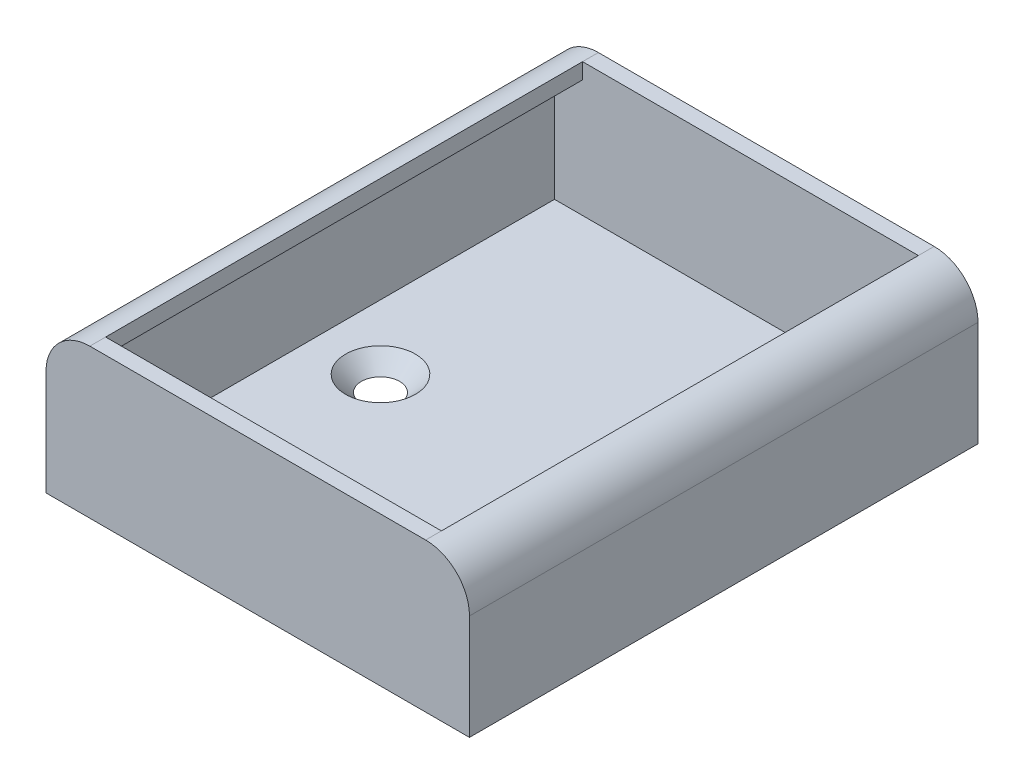
SolidWorks part; units mm, degrees
ref_plane "Front Plane" through (0, 0, 0) normal (0, 0, 1) x (1, 0, 0)
ref_plane "Top Plane" through (0, 0, 0) normal (0, 1, 0) x (1, 0, 0)
ref_plane "Right Plane" through (0, 0, 0) normal (1, 0, 0) x (0, 0, -1)
sketch "Sketch1" plane through (0, 0, 0) normal (0, 1, 0) x (1, 0, 0)
  line L1 (-24.15, -29) -> (24.15, -29)
  line L2 (-24.15, -29) -> (-24.15, 29)
  line L3 (-24.15, 29) -> (24.15, 29)
  line L4 (24.15, -29) -> (24.15, 29)
  line L5 (-24.15, -29) -> (24.15, 29) construction
  line L6 (-24.15, 29) -> (24.15, -29) construction
  point P0 (0, 0)
  point P10 (0, 0)
  point P11 (0, 0)
  point P12 (-62.6961, 27.0611)
  point P13 (0, 0)
  dimension "D1" = 58
  dimension "D2" = 48.3
extrude "Boss-Extrude1" add sketch "Sketch1" along normal blind 17
fillet "Fillet1" radius 5 2 edges at (-24.15, 17, 0) (24.15, 17, 0)
shell "Shell2" thickness 1.8 removed face at (0, 17, 0)
sketch "Sketch2" plane through (0, 1.8, 0) normal (0, 1, 0) x (1, 0, 0)
  circle A0 centre (-15, 0) radius 1.75
  circle A1 centre (15, 0) radius 1.75
  point P4 (0, 0)
  dimension "D1" = 3.5
  dimension "D2" = 3.5
  dimension "D3" = 30
  dimension "D4" = 15
extrude "Cut-Extrude1" cut sketch "Sketch2" against normal blind 17
chamfer "Chamfer1" distance 2.23 angle 45 2 edges at (-15, 1.8, 1.75) (15, 1.8, 1.75)
